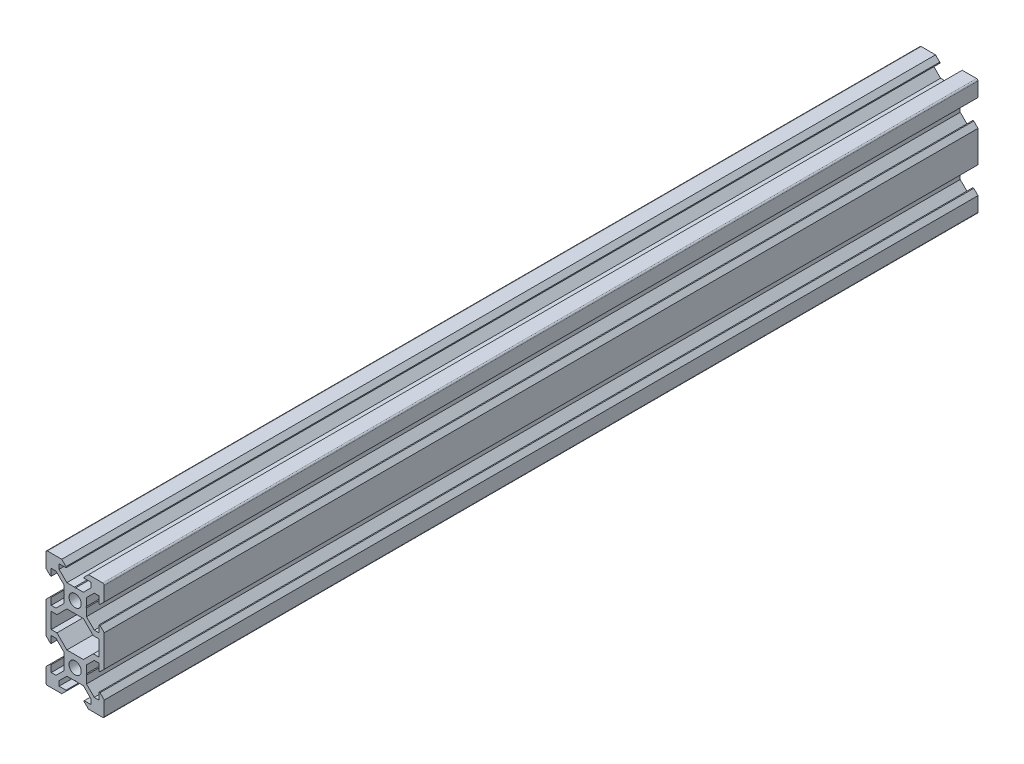
SolidWorks part; units mm, degrees
ref_plane "Front Plane" through (0, 0, 0) normal (0, 0, 1) x (1, 0, 0)
ref_plane "Top Plane" through (0, 0, 0) normal (0, 1, 0) x (1, 0, 0)
ref_plane "Right Plane" through (0, 0, 0) normal (1, 0, 0) x (0, 0, -1)
sketch "Sketch1" plane through (0, 0, 0) normal (0, 0, 1) x (1, 0, 0)
  line L0 (0, 0) -> (10, 0) construction
  line L1 (9.5, -20) -> (-9.5, -20)
  line L2 (10, -19.5) -> (10, 19.5)
  line L3 (9.5, 20) -> (-9.5, 20)
  line L4 (-10, -19.5) -> (-10, 19.5)
  line L5 (10, -20) -> (-10, 20) construction
  line L6 (10, 20) -> (-10, -20) construction
  circle A0 centre (0, 10) radius 2.1
  circle A1 centre (0, -10) radius 2.1
  arc A2 (-9.5, -20) -> (-10, -19.5) centre (-9.5, -19.5) cw
  arc A3 (9.5, -20) -> (10, -19.5) centre (9.5, -19.5) ccw
  arc A4 (10, 19.5) -> (9.5, 20) centre (9.5, 19.5) ccw
  arc A5 (-9.5, 20) -> (-10, 19.5) centre (-9.5, 19.5) ccw
  point P0 (0, 0)
  line B0 (0, 10) -> (0, 20) construction
  line B1 (0, 13.69) -> (-0.21, 13.9)
  line B2 (-0.21, 13.9) -> (-2.8393, 13.9)
  line B3 (-2.8393, 13.9) -> (-5.5, 16.5607)
  line B4 (-5.5, 16.5607) -> (-5.5, 18.2)
  line B5 (-5.5, 18.2) -> (-3.125, 18.2)
  line B6 (-3.125, 18.2) -> (-3.125, 18.545)
  line B7 (-3.125, 18.545) -> (-4.58, 20)
  line B8 (-4.58, 20) -> (4.58, 20)
  line B9 (0, 10) -> (-5.9132, 15.9132) construction
  line B10 (3.125, 18.545) -> (4.58, 20)
  line B11 (3.125, 18.2) -> (3.125, 18.545)
  line B12 (5.5, 18.2) -> (3.125, 18.2)
  line B13 (5.5, 16.5607) -> (5.5, 18.2)
  line B14 (2.8393, 13.9) -> (5.5, 16.5607)
  line B15 (0.21, 13.9) -> (2.8393, 13.9)
  line B16 (0, 13.69) -> (0.21, 13.9)
  line B17 (0, 10) -> (-10, 10) construction
  line B18 (-3.69, 10) -> (-3.9, 9.79)
  line B19 (-3.9, 9.79) -> (-3.9, 7.1607)
  line B20 (-3.9, 7.1607) -> (-6.5607, 4.5)
  line B21 (-6.5607, 4.5) -> (-8.2, 4.5)
  line B22 (-8.2, 4.5) -> (-8.2, 6.875)
  line B23 (-8.2, 6.875) -> (-8.545, 6.875)
  line B24 (-8.545, 6.875) -> (-10, 5.42)
  line B25 (-10, 5.42) -> (-10, 14.58)
  line B26 (0, 10) -> (-5.9132, 4.0868) construction
  line B27 (-8.545, 13.125) -> (-10, 14.58)
  line B28 (-8.2, 13.125) -> (-8.545, 13.125)
  line B29 (-8.2, 15.5) -> (-8.2, 13.125)
  line B30 (-6.5607, 15.5) -> (-8.2, 15.5)
  line B31 (-3.9, 12.8393) -> (-6.5607, 15.5)
  line B32 (-3.9, 10.21) -> (-3.9, 12.8393)
  line B33 (-3.69, 10) -> (-3.9, 10.21)
  line B34 (0, -10) -> (-10, -10) construction
  line B35 (-3.69, -10) -> (-3.9, -10.21)
  line B36 (-3.9, -10.21) -> (-3.9, -12.8393)
  line B37 (-3.9, -12.8393) -> (-6.5607, -15.5)
  line B38 (-6.5607, -15.5) -> (-8.2, -15.5)
  line B39 (-8.2, -15.5) -> (-8.2, -13.125)
  line B40 (-8.2, -13.125) -> (-8.545, -13.125)
  line B41 (-8.545, -13.125) -> (-10, -14.58)
  line B42 (-10, -14.58) -> (-10, -5.42)
  line B43 (0, -10) -> (-5.9132, -15.9132) construction
  line B44 (-8.545, -6.875) -> (-10, -5.42)
  line B45 (-8.2, -6.875) -> (-8.545, -6.875)
  line B46 (-8.2, -4.5) -> (-8.2, -6.875)
  line B47 (-6.5607, -4.5) -> (-8.2, -4.5)
  line B48 (-3.9, -7.1607) -> (-6.5607, -4.5)
  line B49 (-3.9, -9.79) -> (-3.9, -7.1607)
  line B50 (-3.69, -10) -> (-3.9, -9.79)
  line B51 (0, -10) -> (0, -20) construction
  line B52 (0, -13.69) -> (0.21, -13.9)
  line B53 (0.21, -13.9) -> (2.8393, -13.9)
  line B54 (2.8393, -13.9) -> (5.5, -16.5607)
  line B55 (5.5, -16.5607) -> (5.5, -18.2)
  line B56 (5.5, -18.2) -> (3.125, -18.2)
  line B57 (3.125, -18.2) -> (3.125, -18.545)
  line B58 (3.125, -18.545) -> (4.58, -20)
  line B59 (4.58, -20) -> (-4.58, -20)
  line B60 (0, -10) -> (5.9132, -15.9132) construction
  line B61 (-3.125, -18.545) -> (-4.58, -20)
  line B62 (-3.125, -18.2) -> (-3.125, -18.545)
  line B63 (-5.5, -18.2) -> (-3.125, -18.2)
  line B64 (-5.5, -16.5607) -> (-5.5, -18.2)
  line B65 (-2.8393, -13.9) -> (-5.5, -16.5607)
  line B66 (-0.21, -13.9) -> (-2.8393, -13.9)
  line B67 (0, -13.69) -> (-0.21, -13.9)
  line B68 (0, -10) -> (10, -10) construction
  line B69 (3.69, -10) -> (3.9, -9.79)
  line B70 (3.9, -9.79) -> (3.9, -7.1607)
  line B71 (3.9, -7.1607) -> (6.5607, -4.5)
  line B72 (6.5607, -4.5) -> (8.2, -4.5)
  line B73 (8.2, -4.5) -> (8.2, -6.875)
  line B74 (8.2, -6.875) -> (8.545, -6.875)
  line B75 (8.545, -6.875) -> (10, -5.42)
  line B76 (10, -5.42) -> (10, -14.58)
  line B77 (0, -10) -> (5.9132, -4.0868) construction
  line B78 (8.545, -13.125) -> (10, -14.58)
  line B79 (8.2, -13.125) -> (8.545, -13.125)
  line B80 (8.2, -15.5) -> (8.2, -13.125)
  line B81 (6.5607, -15.5) -> (8.2, -15.5)
  line B82 (3.9, -12.8393) -> (6.5607, -15.5)
  line B83 (3.9, -10.21) -> (3.9, -12.8393)
  line B84 (3.69, -10) -> (3.9, -10.21)
  line B85 (0, 10) -> (10, 10) construction
  line B86 (3.69, 10) -> (3.9, 10.21)
  line B87 (3.9, 10.21) -> (3.9, 12.8393)
  line B88 (3.9, 12.8393) -> (6.5607, 15.5)
  line B89 (6.5607, 15.5) -> (8.2, 15.5)
  line B90 (8.2, 15.5) -> (8.2, 13.125)
  line B91 (8.2, 13.125) -> (8.545, 13.125)
  line B92 (8.545, 13.125) -> (10, 14.58)
  line B93 (10, 14.58) -> (10, 5.42)
  line B94 (0, 10) -> (5.9132, 15.9132) construction
  line B95 (8.545, 6.875) -> (10, 5.42)
  line B96 (8.2, 6.875) -> (8.545, 6.875)
  line B97 (8.2, 4.5) -> (8.2, 6.875)
  line B98 (6.5607, 4.5) -> (8.2, 4.5)
  line B99 (3.9, 7.1607) -> (6.5607, 4.5)
  line B100 (3.9, 9.79) -> (3.9, 7.1607)
  line B101 (3.69, 10) -> (3.9, 9.79)
  line B102 (-8.2, -2.7) -> (-8.2, 2.7)
  line B103 (-8.2, 2.7) -> (-6.2393, 2.7)
  line B104 (-6.2393, 2.7) -> (-2.8393, 6.1)
  line B105 (-2.8393, 6.1) -> (2.8393, 6.1)
  line B106 (0, 6.1) -> (0, 0) construction
  line B107 (0, 0) -> (-8.2, 0) construction
  line B108 (6.2393, 2.7) -> (2.8393, 6.1)
  line B109 (8.2, 2.7) -> (6.2393, 2.7)
  line B110 (8.2, -2.7) -> (8.2, 2.7)
  line B111 (8.2, -2.7) -> (6.2393, -2.7)
  line B112 (6.2393, -2.7) -> (2.8393, -6.1)
  line B113 (-2.8393, -6.1) -> (2.8393, -6.1)
  line B114 (-6.2393, -2.7) -> (-2.8393, -6.1)
  line B115 (-8.2, -2.7) -> (-6.2393, -2.7)
  line B116 (0, 6.1) -> (0, 10) construction
  line B117 (0, 10) -> (-5.0927, 4.9073) construction
  dimension "D4" = 4.2
  dimension "D5" = 0.5
  dimension "D1" = 20
  dimension "D2" = 40
  dimension "D3" = 20
sketch_block_instance "V Slot 1-4"
sketch_block "V Slot 1" parameters "D1"=10, "D2"=11, "D3"=4.3, "D4"=1.8, "D5"=0.21, "D6"=45, "D7"=9.16, "D8"=1.5, "D9"=6.25
sketch_block_instance "V Slot 1-5"
sketch_block_instance "V Slot 1-6"
sketch_block_instance "V Slot 1-7"
sketch_block_instance "V Slot 1-8"
sketch_block_instance "V Slot 1-9"
sketch_block_instance "Center Cutout 1-1"
sketch_block "Center Cutout 1" parameters "D1"=5.4, "D2"=12.2, "D3"=8.2, "D4"=45, "D5"=10, "D6"=1.5
extrude "Boss-Extrude1" add sketch "Sketch1" along normal blind 300 contours B101 B86 B87 B88 B89 B90 B91 B92 L2 A4 L3 B10 B11 B12 B13 B14 B15 B16 B1 B2 B3 B4 B5 B6 B7 A5 L4 B27 B28 B29 B30 B31 B32 B33 B18 B19 B20 B21 B22 B23 B24 B44 B45 B46 B47 B48 B49 B50 B35 region at (7.04, -19.5528, 0)
